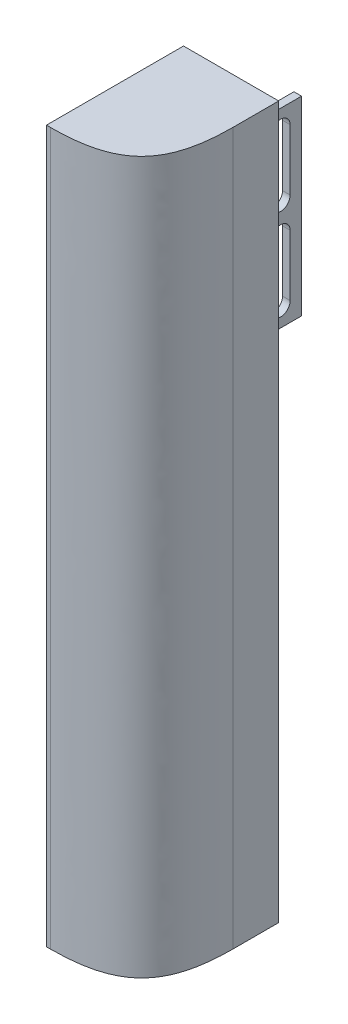
SolidWorks part; units mm, degrees
ref_plane "Front Plane" through (0, 0, 0) normal (0, 0, 1) x (1, 0, 0)
ref_plane "Top Plane" through (0, 0, 0) normal (0, 1, 0) x (1, 0, 0)
ref_plane "Right Plane" through (0, 0, 0) normal (1, 0, 0) x (0, 0, -1)
sketch "Sketch1" plane through (0, 0, 0) normal (0, 1, 0) x (1, 0, 0)
  line L1 (0, 0) -> (25, 0)
  line L2 (0, 0) -> (0, 36)
  line L3 (0, 36) -> (25, 36)
  line L4 (25, 0) -> (25, 36)
  dimension "D1" = 36
  dimension "D2" = 25
extrude "Boss-Extrude1" add sketch "Sketch1" along normal blind 186.9
fillet "Fillet1" radius 24 1 edges at (25, 93.45, 0) conic rho 0.55
sketch "Sketch2" plane through (0, 0, 0) normal (-1, 0, 0) x (0, 0, 1)
  line L0 (-24, 0) -> (0, 0) construction
  line L1 (-6.2, 83.2) -> (-1.2, 83.2)
  line L2 (-6.2, 83.2) -> (-6.2, 73.2)
  line L3 (-6.2, 73.2) -> (-1.2, 73.2)
  line L4 (-1.2, 83.2) -> (-1.2, 73.2)
  line L5 (0, 186.9) -> (0, 0) construction
  dimension "D1" = 73.2
  dimension "D2" = 1.2
  dimension "D3" = 5
  dimension "D4" = 10
extrude "Cut-Extrude1" cut sketch "Sketch2" against normal blind 4
sketch "Sketch3" plane through (0, 0, 0) normal (-1, 0, 0) x (0, 0, 1)
  line L1 (-14, 33.2) -> (-6, 33.2)
  line L2 (-14, 33.2) -> (-14, 28)
  line L3 (-14, 28) -> (-6, 28)
  line L4 (-6, 33.2) -> (-6, 28)
  line L5 (-36, 0) -> (0, 0) construction
  line L6 (0, 186.9) -> (0, 0) construction
  line L8 (-22, 33.2) -> (-30, 33.2)
  line L9 (-22, 33.2) -> (-22, 28)
  line L10 (-22, 28) -> (-30, 28)
  line L11 (-30, 33.2) -> (-30, 28)
  line L12 (-6, 61.2) -> (-14, 61.2)
  line L13 (-6, 61.2) -> (-6, 66.8)
  line L14 (-6, 66.8) -> (-14, 66.8)
  line L15 (-14, 61.2) -> (-14, 66.8)
  line L16 (-22, 66.8) -> (-30, 66.8)
  line L17 (-22, 66.8) -> (-22, 61.2)
  line L18 (-22, 61.2) -> (-30, 61.2)
  line L19 (-30, 66.8) -> (-30, 61.2)
  dimension "D1" = 28
  dimension "D2" = 6
  dimension "D3" = 8
  dimension "D4" = 5.2
  dimension "D5" = 8
  dimension "D6" = 8
  dimension "D7" = 28
  dimension "D8" = 5.6
  dimension "D9" = 8
  dimension "D10" = 6
  dimension "D11" = 8
  dimension "D12" = 5.6
  dimension "D13" = 8
extrude "Cut-Extrude2" cut sketch "Sketch3" against normal blind 10
sketch "Sketch4" plane through (0, 0, 0) normal (-1, 0, 0) x (0, 0, 1)
  line L0 (-36, 0) -> (0, 0) construction
  line L1 (-26, 160) -> (-67, 160)
  line L2 (-26, 160) -> (-26, 110)
  line L3 (-26, 110) -> (-67, 110)
  line L4 (-67, 160) -> (-67, 110)
  line L5 (-36, 186.9) -> (-36, 0) construction
  dimension "D1" = 160
  dimension "D2" = 10
  dimension "D3" = 31
  dimension "D4" = 110
extrude "Boss-Extrude2" add sketch "Sketch4" along normal blind 2
sketch "Sketch5" plane through (-2, 0, 0) normal (-1, 0, 0) x (0, 0, 1)
  line L0 (-67, 110) -> (-26, 110) construction
  line L1 (-67, 160) -> (-67, 110) construction
  line L4 (-59, 131) -> (-59, 115)
  line L6 (-64, 131) -> (-64, 115)
  line L7 (-26, 160) -> (-67, 160) construction
  line L9 (-64, 139) -> (-64, 155)
  line L11 (-59, 139) -> (-59, 155)
  arc A0 (-64, 115) -> (-59, 115) centre (-61.5, 115) ccw
  arc A2 (-59, 131) -> (-64, 131) centre (-61.5, 131) ccw
  arc A3 (-59, 155) -> (-64, 155) centre (-61.5, 155) ccw
  arc A4 (-64, 139) -> (-59, 139) centre (-61.5, 139) ccw
  dimension "D1" = 5
  dimension "D4" = 16
  dimension "D5" = 16
  dimension "D2" = 5
  dimension "D3" = 5.5
  dimension "D6" = 5
extrude "Cut-Extrude3" cut sketch "Sketch5" against normal up to next
chamfer "Chamfer1" distance 16 angle 45 1 edges at (0, 135, -36)
